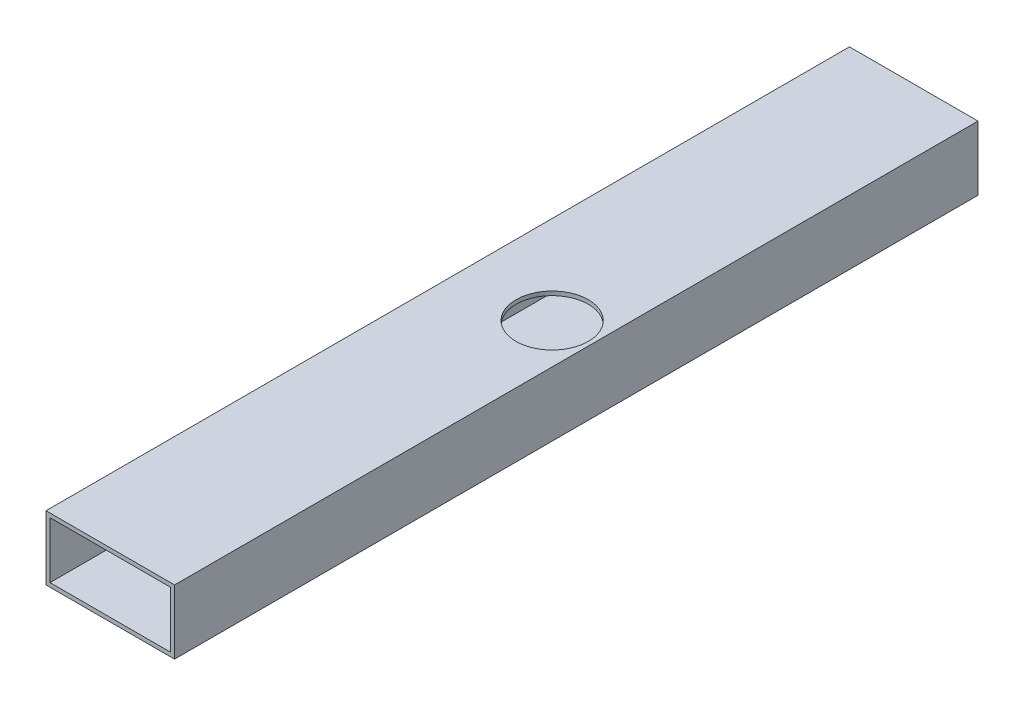
SolidWorks part; units mm, degrees
ref_plane "Front Plane" through (0, 0, 0) normal (0, 0, 1) x (1, 0, 0)
ref_plane "Top Plane" through (0, 0, 0) normal (0, 1, 0) x (1, 0, 0)
ref_plane "Right Plane" through (0, 0, 0) normal (1, 0, 0) x (0, 0, -1)
sketch "Sketch1" plane through (0, 0, 0) normal (0, 0, 1) x (1, 0, 0)
  line L0 (-23.8125, 11.1125) -> (23.8125, 11.1125)
  line L2 (-25.4, 12.7) -> (25.4, 12.7)
  line L3 (-25.4, 12.7) -> (-25.4, -12.7)
  line L4 (-25.4, -12.7) -> (25.4, -12.7)
  line L5 (25.4, 12.7) -> (25.4, -12.7)
  line L10 (23.8125, 11.1125) -> (23.8125, -11.1125)
  line L11 (-23.8125, -11.1125) -> (23.8125, -11.1125)
  line L12 (-23.8125, 11.1125) -> (-23.8125, -11.1125)
  point P12 (0, 12.7)
  point P14 (25.4, 0)
  dimension "Wall Thickness" = 1.5875
  dimension "Outside Width" = 50.8
  dimension "Outside Height" = 25.4
  dimension "Inside Height" = 22.225
  dimension "Inside Width" = 47.625
sketch "Sketch2" plane through (0, 0, 0) normal (1, 0, 0) x (0, 0, -1)
  line L0 (158.75, 0) -> (-158.75, 0)
  point P4 (0, 0)
  point P7 (-158.75, 0)
  point P10 (158.75, 0)
  dimension "Length" = 317.5
sketch "Sketch3" plane through (0, 0, 0) normal (0, 0, 1) x (1, 0, 0)
  line L21 (25.4, 12.7) -> (-25.4, 12.7)
  line L22 (25.4, -12.7) -> (25.4, 12.7)
  line L23 (-25.4, -12.7) -> (25.4, -12.7)
  line L24 (-25.4, 12.7) -> (-25.4, -12.7)
  line L25 (25.4, 12.7) -> (-25.4, 12.7)
  line L26 (25.4, -12.7) -> (25.4, 12.7)
  line L27 (-25.4, -12.7) -> (25.4, -12.7)
  line L28 (-25.4, 12.7) -> (-25.4, -12.7)
  line L29 (23.8125, 11.1125) -> (-23.8125, 11.1125)
  line L30 (23.8125, -11.1125) -> (23.8125, 11.1125)
  line L31 (-23.8125, -11.1125) -> (23.8125, -11.1125)
  line L32 (-23.8125, 11.1125) -> (-23.8125, -11.1125)
  line L33 (23.8125, 11.1125) -> (-23.8125, 11.1125)
  line L34 (23.8125, -11.1125) -> (23.8125, 11.1125)
  line L35 (-23.8125, -11.1125) -> (23.8125, -11.1125)
  line L36 (-23.8125, 11.1125) -> (-23.8125, -11.1125)
  dimension "D1" = 0
  dimension "D2" = 0
extrude "Boss-Extrude1" add sketch "Sketch3" along normal up to vertex (158.75 mm away) and the other way up to vertex (158.75 mm away) up to point (0, 0, 158.75) other way up to point (0, 0, -158.75)
sketch "Drawing Reference" plane through (0, 0, 0) normal (1, 0, 0) x (0, 0, -1)
  line L0 (-158.75, 0) -> (158.75, 0) construction
  line L1 (0, -12.7) -> (0, 12.7) construction
  line L2 (-158.75, -12.7) -> (158.75, -12.7) construction
  line L5 (-158.75, 12.7) -> (158.75, 12.7) construction
  point P7 (-122.174, 0)
  point P8 (122.174, 0)
  dimension "D1" = 36.576
sketch "Sketch4" plane through (0, 12.7, 0) normal (0, 1, 0) x (1, 0, 0)
  line L0 (0, 158.75) -> (0, 6.35) construction
  line L1 (25.4, 158.75) -> (-25.4, 158.75) construction
  line L2 (0, 6.35) -> (9.525, 6.35) construction
  circle A1 centre (9.525, 6.35) radius 14.2875
  dimension "D1" = 152.4
  dimension "D2" = 9.525
extrude "Cut-Extrude1" cut sketch "Sketch4" against normal blind 39.37
equation "\"D1@Drawing Reference\"=\"Outside Width@Sketch1\" * 0.72"
